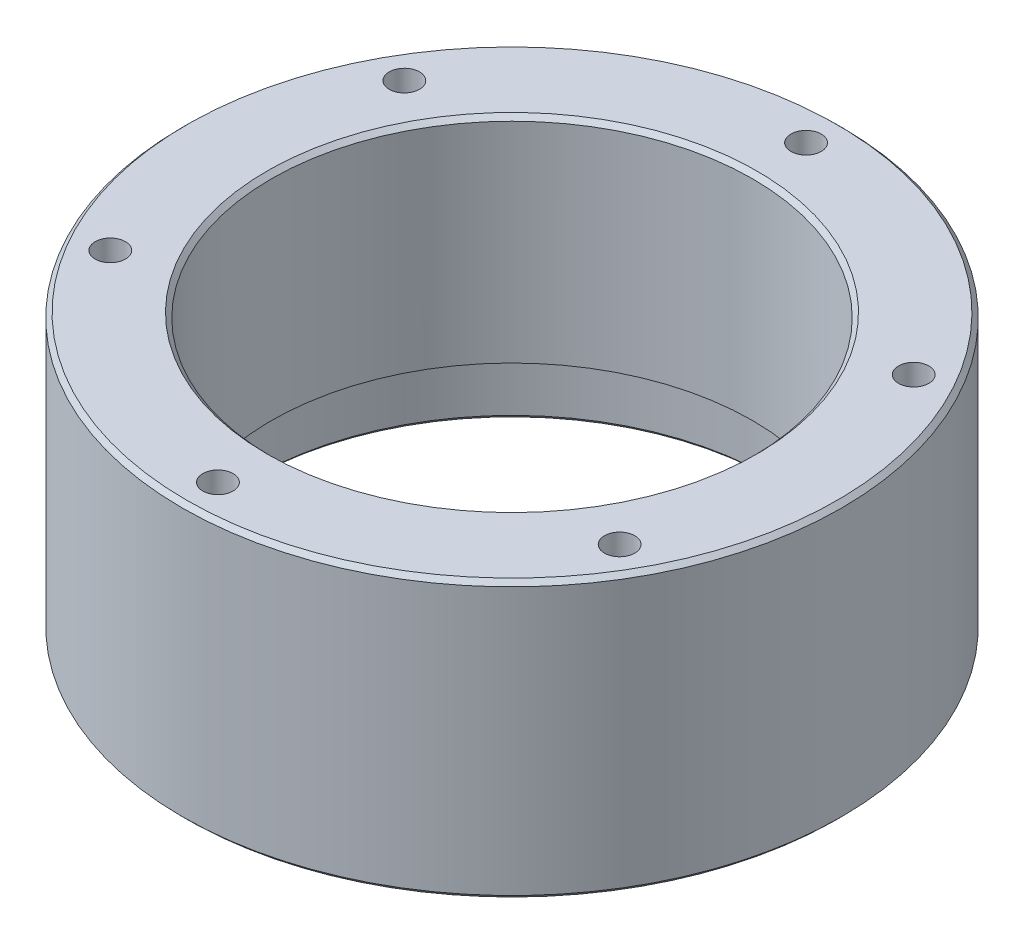
SolidWorks part; units mm, degrees
ref_plane "Ebene vorne" through (0, 0, 0) normal (0, 0, 1) x (1, 0, 0)
ref_plane "Ebene oben" through (0, 0, 0) normal (0, 1, 0) x (1, 0, 0)
ref_plane "Ebene rechts" through (0, 0, 0) normal (1, 0, 0) x (0, 0, -1)
sketch "Sketch1" plane through (0, 0, 0) normal (0, 0, 1) x (1, 0, 0)
  line L0 (0, 0) -> (0, 50) construction
  line L1 (29, 0) -> (37, 0)
  line L2 (37, 0) -> (37, 31)
  line L3 (37, 31) -> (27, 31)
  line L4 (27, 31) -> (27, 7)
  line L5 (27, 7) -> (29, 7)
  line L6 (29, 7) -> (29, 0)
  dimension "D1" = 50
  dimension "D2" = 58
  dimension "D3" = 2
  dimension "D4" = 24
  dimension "D5" = 7
  dimension "D6" = 8
revolve "Revolve1" add sketch "Sketch1" angle 360 about L0
hole_wizard "CBORE for M3 Hex Socket Head Cap Screw1" positions "Sketch2" profile "Sketch3" counterbore size "M3" standard "DIN" end condition through all
sketch "Sketch2" plane through (0, 0, 0) normal (0, -1, 0) x (-1, 0, 0)
  line L0 (0, -29) -> (0, -37) construction
  circle A0 centre (0, 0) radius 29 construction
  circle A1 centre (0, 0) radius 29 construction
  circle A2 centre (0, 0) radius 37 construction
  point P12 (0, -33)
  point P22 (-28.5788, -16.5)
  point P23 (-28.5788, 16.5)
  point P24 (0, 33)
  point P25 (28.5788, 16.5)
  point P26 (28.5788, -16.5)
  dimension "D1" = 6
sketch "Sketch3" plane through (-28.5788, 0, 16.5) normal (1, 0, 0) x (0, 0, -1)
  line L0 (0, 0) -> (0, 31)
  line L1 (0, 31) -> (1.7, 31)
  line L3 (1.7, 31) -> (1.7, 3.4)
  line L4 (1.7, 3.4) -> (3.25, 3.4)
  line L5 (3.25, 3.4) -> (3.25, 0)
  line L7 (3.25, 0) -> (0, 0)
  line L11 (0, -6.35) -> (0, 107.95) construction
  dimension "Thru Hole Dia." = 3.4
  dimension "Thru Hole Depth" = 31
  dimension "C'Bore Dia." = 6.5
  dimension "C'Bore Depth" = 3.4
chamfer "0,5mm Chamfer1" distance 0.5 angle 45 4 edges at (0, 31, -27) (0, 31, -37) (0, 0, -37) (0, 0, -29)
